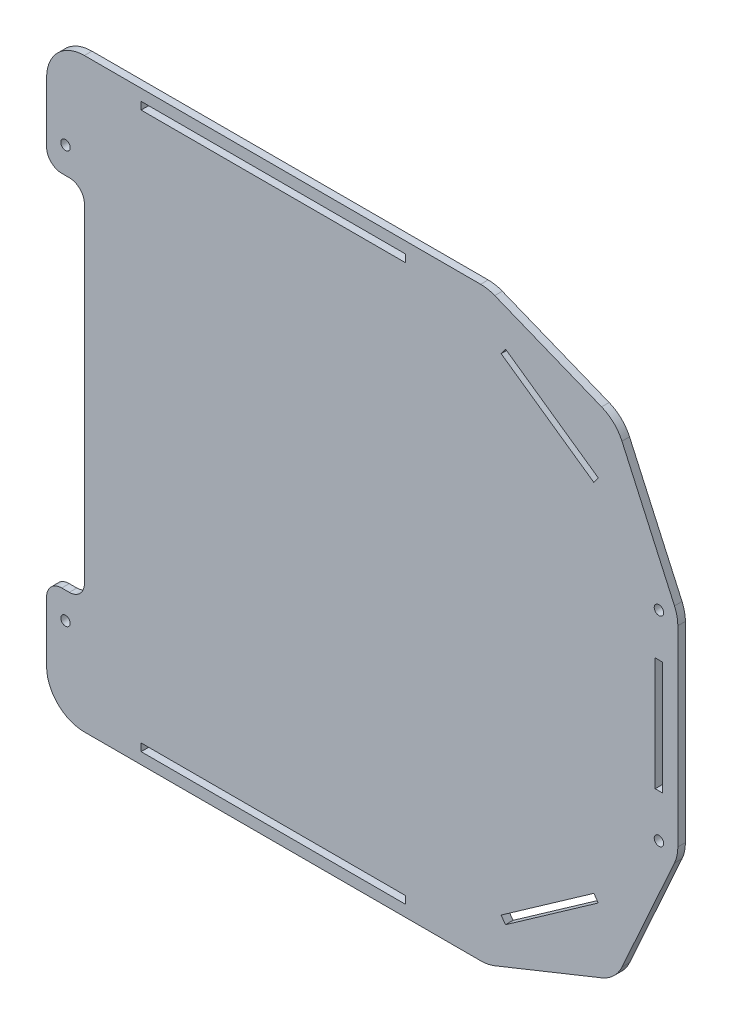
SolidWorks part; units mm, degrees
material "PVC rigido"
ref_plane "Piano frontale" through (0, 0, 0) normal (0, 0, 1) x (1, 0, 0)
ref_plane "Piano superiore" through (0, 0, 0) normal (0, 1, 0) x (1, 0, 0)
ref_plane "Piano destro" through (0, 0, 0) normal (1, 0, 0) x (0, 0, -1)
sketch "Schizzo1" plane through (0, 0, 0) normal (0, 0, 1) x (1, 0, 0)
  line L0 (25.7647, -77.5) -> (59.5674, -63.9093)
  line L1 (-91, -77.5) -> (25.7647, -77.5)
  line L2 (-91, -77.5) -> (-91, 77.5)
  line L3 (-91, 77.5) -> (25.7647, 77.5)
  line L4 (76, -27.5) -> (76, 27.5)
  line L5 (69.2392, 67.1366) -> (85.1147, 31.9616) construction
  line L6 (59.5674, -63.9093) -> (59.5674, 63.9093) construction
  line L7 (59.5674, -63.9093) -> (76, -27.5)
  line L8 (25.7647, 77.5) -> (59.5674, 63.9093)
  line L9 (59.5674, 63.9093) -> (76, 27.5)
  line L10 (25.7647, 77.5) -> (76, 77.5) construction
  line L11 (76, 77.5) -> (76, 27.5) construction
  line L12 (25.7647, -77.5) -> (76, -77.5) construction
  line L13 (76, -77.5) -> (76, -27.5) construction
  line L14 (63.8549, -72.3011) -> (27.8474, -86.7782) construction
  line L15 (85.1147, -31.9616) -> (69.2392, -67.1366) construction
  line L16 (27.8474, 86.7782) -> (63.8549, 72.3011) construction
  line L17 (0, 0) -> (25.7647, 77.5) construction
  line L18 (0, 0) -> (25.7647, -77.5) construction
  line L19 (25.7647, -77.5) -> (25.7647, 77.5) construction
  line L20 (-91, -77.5) -> (0, 0) construction
  line L21 (0, 0) -> (-91, 77.5) construction
  line L22 (0, 0) -> (-91, 0) construction
  line L23 (0, 0) -> (0, 77.5) construction
  line L24 (86, 27.8479) -> (86, -27.8479) construction
  point P0 (0, 0)
  dimension "D1" = 155
  dimension "D2" = 91
  dimension "D3" = 55
  dimension "D4" = 10
extrude "Estrusione-Estrusione1" add sketch "Schizzo1" along normal blind 2
hole_wizard "Foro filettato M3x0.5-1" positions "Schizzo3" profile "Schizzo2" tap size "M3x0.5" standard "Ansi Metric" end condition through all
sketch "Schizzo3" plane through (0, 0, 0) normal (0, 0, -1) x (-1, 0, 0)
  line L0 (86, -77.5) -> (86, -54.5) construction
  line L1 (91, -77.5) -> (-25.7647, -77.5) construction
  line L2 (86, -54.5) -> (86, 54.5) construction
  line L3 (86, 54.5) -> (86, 77.5) construction
  line L4 (-25.7647, 77.5) -> (91, 77.5) construction
  line L6 (0, 0) -> (86, 0) construction
  point P0 (86, -54.5)
  point P2 (86, 54.5)
sketch "Schizzo2" plane through (-86, -54.5, 0) normal (1, 0, 0) x (0, 1, 0)
  line L0 (0, 0) -> (0, 2)
  line L1 (0, 2) -> (1.25, 2)
  line L2 (1.25, 2) -> (1.25, 0)
  line L5 (1.25, 0) -> (0, 0)
  line L11 (0, -6.35) -> (0, 107.95) construction
  dimension "Thru Tap Drill Dia." = 2.5
  dimension "Thru Tap Drill Depth" = 2
cosmetic thread "Filettatura del foro1" parameters "D2"=3
cosmetic thread "Filettatura del foro2" parameters "D2"=3
sketch "Schizzo4" plane through (0, 0, 0) normal (0, 0, -1) x (-1, 0, 0)
  line L0 (31, -72.5) -> (31, 72.5) construction
  line L1 (66, -74.5) -> (-4, -74.5)
  line L2 (66, -74.5) -> (66, -72.5)
  line L3 (66, -72.5) -> (-4, -72.5)
  line L4 (-4, -74.5) -> (-4, -72.5)
  line L5 (66, 72.5) -> (-4, 72.5)
  line L6 (66, 72.5) -> (66, 74.5)
  line L7 (66, 74.5) -> (-4, 74.5)
  line L8 (-4, 72.5) -> (-4, 74.5)
  line L9 (31, 0) -> (91, 0) construction
  line L10 (91, 77.5) -> (91, -77.5) construction
  line L11 (91, -77.5) -> (-25.7647, -77.5) construction
  dimension "D1" = 2
  dimension "D2" = 3
  dimension "D3" = 70
  dimension "D4" = 60
extrude "Taglio-Estrusione1" cut sketch "Schizzo4" against normal blind 10
hole_wizard "Foro filettato M3x0.5-2" positions "Schizzo6" profile "Schizzo5" tap size "M3x0.5" standard "Ansi Metric" end condition through all
sketch "Schizzo6" plane through (0, 0, 2) normal (0, 0, 1) x (1, 0, 0)
  line L16 (55.0101, -61.8525) -> (71, -26.4239)
  line L17 (71, -26.4239) -> (71, 26.4239)
  line L18 (71, 26.4239) -> (55.0101, 61.8525)
  line L19 (55.0101, -61.8525) -> (71, -26.4239) construction
  line L20 (71, -26.4239) -> (71, 26.4239) construction
  line L21 (71, 26.4239) -> (55.0101, 61.8525) construction
  point P0 (71, 26.4239)
  point P2 (71, -26.4239)
  dimension "D1" = 5
sketch "Schizzo5" plane through (71, 26.4239, 2) normal (1, 0, 0) x (0, -1, 0)
  line L0 (0, 0) -> (0, 2)
  line L1 (0, 2) -> (1.25, 2)
  line L2 (1.25, 2) -> (1.25, 0)
  line L5 (1.25, 0) -> (0, 0)
  line L11 (0, -6.35) -> (0, 107.95) construction
  dimension "Thru Tap Drill Dia." = 2.5
  dimension "Thru Tap Drill Depth" = 2
cosmetic thread "Filettatura del foro3" parameters "D2"=3
cosmetic thread "Filettatura del foro4" parameters "D2"=3
sketch "Schizzo7" plane through (0, 0, 2) normal (0, 0, 1) x (1, 0, 0)
  line L0 (30.4008, 65.9495) -> (54.9474, 48.7024)
  line L1 (53.7976, 47.0659) -> (29.251, 64.3131)
  line L2 (29.251, 64.3131) -> (30.4008, 65.9495)
  line L3 (53.7976, 47.0659) -> (54.9474, 48.7024)
  line L4 (71, 26.4239) -> (4, 73.5) construction
  line L5 (4, 74.5) -> (4, 72.5) construction
  line L6 (4, 74.5) -> (4, 72.5) construction
  line L7 (29.8259, 65.1313) -> (54.3725, 47.8842) construction
  line L8 (42.0992, 56.5077) -> (37.5, 49.962) construction
  line L9 (71, 26.4239) -> (71, 15) construction
  line L10 (71, 15) -> (71, -15) construction
  line L11 (71, -15) -> (71, -26.4239) construction
  line L12 (71, -26.4239) -> (4, -73.5) construction
  line L15 (4, -72.5) -> (4, -74.5) construction
  line L16 (53.7976, -47.0659) -> (29.251, -64.3131)
  line L17 (29.251, -64.3131) -> (30.4008, -65.9495)
  line L18 (30.4008, -65.9495) -> (54.9474, -48.7024)
  line L19 (54.9474, -48.7024) -> (53.7976, -47.0659)
  line L20 (54.3725, -47.8842) -> (29.8259, -65.1313) construction
  line L21 (37.5, -49.962) -> (42.0992, -56.5077) construction
  line L23 (72, -15) -> (70, -15)
  line L24 (72, -15) -> (72, 15)
  line L25 (72, 15) -> (70, 15)
  line L26 (70, -15) -> (70, 15)
  dimension "D1" = 30
  dimension "D2" = 8
  dimension "D3" = 30
extrude "Taglio-Estrusione2" cut sketch "Schizzo7" against normal blind 10
sketch "Schizzo8" plane through (0, 0, 2) normal (0, 0, 1) x (1, 0, 0)
  line L0 (-91, 77.5) -> (-91, -77.5) construction
  line L1 (-91, -47.5) -> (-81, -47.5)
  line L2 (-91, -47.5) -> (-91, 47.5)
  line L3 (-91, 47.5) -> (-81, 47.5)
  line L4 (-81, -47.5) -> (-81, 47.5)
  line L5 (-86, -54.5) -> (-86, -47.5) construction
  line L6 (-86, 54.5) -> (-86, 47.5) construction
  dimension "D1" = 95
extrude "Taglio-Estrusione3" cut sketch "Schizzo8" against normal blind 10
fillet "Raccordo1" radius 10 2 edges at (-91, 77.5, 1) (-91, -77.5, 1)
fillet "Raccordo2" radius 10 6 edges at (25.7647, -77.5, 1) (59.5674, -63.9093, 1) (76, -27.5, 1) (76, 27.5, 1) (59.5674, 63.9093, 1) (25.7647, 77.5, 1)
fillet "Raccordo3" radius 4 4 edges at (-81, 47.5, 1) (-91, 47.5, 1) (-81, -47.5, 1) (-91, -47.5, 1)
